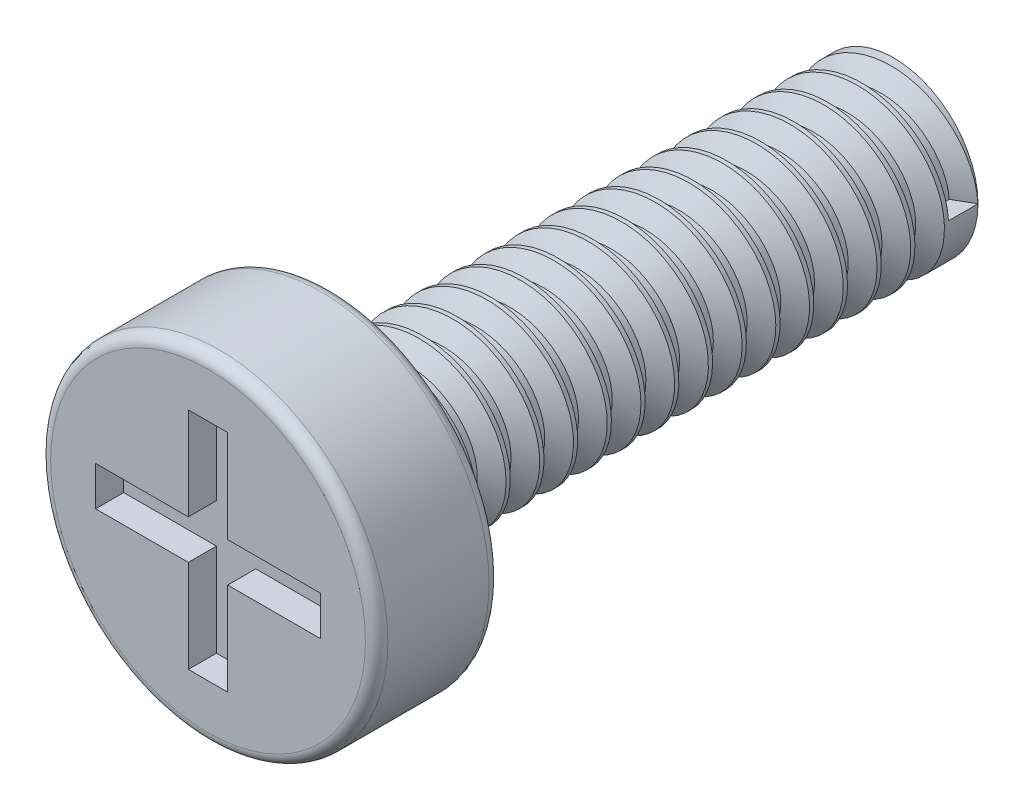
SolidWorks part; units mm, degrees
ref_plane "Front Plane" through (0, 0, 0) normal (0, 0, 1) x (1, 0, 0)
ref_plane "Top Plane" through (0, 0, 0) normal (0, 1, 0) x (1, 0, 0)
ref_plane "Right Plane" through (0, 0, 0) normal (1, 0, 0) x (0, 0, -1)
sketch "Sketch1" plane through (0, 0, 0) normal (0, 0, 1) x (1, 0, 0)
  circle A0 centre (0, 0) radius 1.5
  dimension "D1" = 3
extrude "Boss-Extrude1" add sketch "Sketch1" along normal blind 10
sketch "Sketch2" plane through (0, 0, 10) normal (0, 0, 1) x (1, 0, 0)
  circle A0 centre (0, 0) radius 3
  dimension "D1" = 6
extrude "Boss-Extrude2" add sketch "Sketch2" along normal blind 2.2
sketch "Sketch7" plane through (0, 0, 12.2) normal (0, 0, 1) x (1, 0, 0)
  line L1 (0.35, 2) -> (-0.35, 2)
  line L2 (0.35, 2) -> (0.35, -2)
  line L3 (0.35, -2) -> (-0.35, -2)
  line L4 (-0.35, 2) -> (-0.35, -2)
  line L5 (0, -2) -> (0, 2) construction
  line L6 (0.35, 0) -> (-0.35, 0) construction
  line L7 (2, -0.35) -> (-2, -0.35)
  line L8 (2, -0.35) -> (2, 0.35)
  line L9 (2, 0.35) -> (-2, 0.35)
  line L10 (-2, -0.35) -> (-2, 0.35)
  line L11 (0, 0.35) -> (0, -0.35) construction
  line L12 (2, 0) -> (-2, 0) construction
  point P0 (0, 0)
  point P4 (0, 0)
  dimension "D1" = 4
  dimension "D2" = 0.7
extrude "Cut-Extrude1" cut sketch "Sketch7" against normal blind 0.5 contours L9 L2 L1 L4 | L8 L9 L2 L7 | L2 L7 L4 L3 | L10 L7 L4 L9 | L2 L9 L4 L7 region at (0, 1.175, 12.2) region at (1.175, 0, 12.2) region at (0, 0, 12.2) region at (-1.175, 0, 12.2) region at (0, -1.175, 12.2)
fillet "Fillet1" radius 0.2 2 edges at (3, 0, 12.2) (3, 0, 10)
thread "Thread1" pitch 0.6 method cut profile "Thread Profile1" start angle 0, offset 0, length 0, pitch 0.6, diameter 3
ref_plane "Plane1" through (1.5, 0, 0) normal (0, -1, 0) x (1, 0, 0)
sketch "Thread Profile1" plane through (1.5, 0, 0) normal (0, -1, 0) x (1, 0, 0)
  line L0 (0, 0) -> (0, 0.6) construction
  line L11 (0, 0) -> (0, 0.525)
  line L12 (0, 0.525) -> (-0.3248, 0.3375)
  line L13 (-0.3248, 0.3375) -> (-0.3248, 0.1875)
  line L15 (-0.3248, 0.1875) -> (0, 0)
  line L17 (-0.3248, 0.2625) -> (0, 0.2625) construction
  point P2 (0, 0)
  dimension "Pitch" = 0.6
  dimension "Profile_Angle" = 60
  dimension "Profile_Land" = 0.15
  dimension "Profile_Height" = 0.3248
